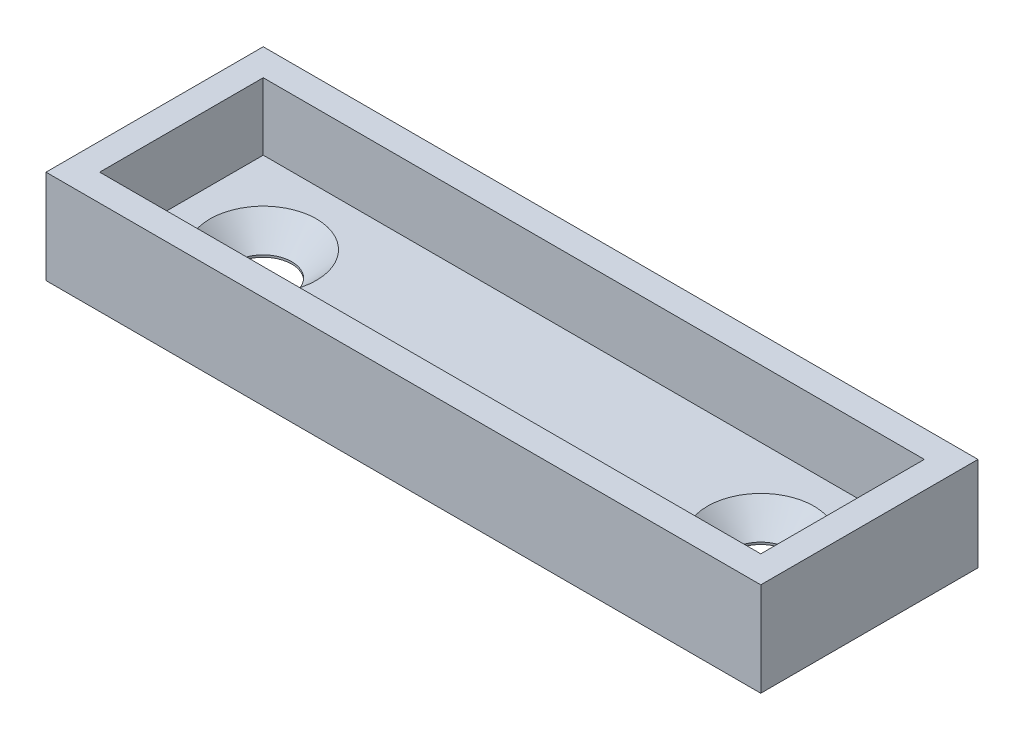
SolidWorks part; units mm, degrees
ref_plane "Front" through (0, 0, 0) normal (0, 0, 1) x (1, 0, 0)
ref_plane "Top" through (0, 0, 0) normal (0, 1, 0) x (1, 0, 0)
ref_plane "Right" through (0, 0, 0) normal (1, 0, 0) x (0, 0, -1)
sketch "Sketch1" plane through (0, 0, 0) normal (0, 1, 0) x (1, 0, 0)
  line L1 (-24.638, -6.096) -> (24.638, -6.096)
  line L2 (-24.638, -6.096) -> (-24.638, 6.096)
  line L3 (-24.638, 6.096) -> (24.638, 6.096)
  line L4 (24.638, -6.096) -> (24.638, 6.096)
  line L5 (-24.638, -6.096) -> (24.638, 6.096) construction
  line L6 (-24.638, 6.096) -> (24.638, -6.096) construction
  point P0 (0, 0)
  point P8 (23.1563, -0.1012)
  dimension "D1" = 12.192
  dimension "D2" = 49.276
extrude "Boss-Extrude1" add sketch "Sketch1" along normal blind 2
sketch "Sketch2" plane through (0, 0, 0) normal (0, 1, 0) x (1, 0, 0)
  line L0 (24.638, 6.096) -> (26.638, 8.096) construction
  line L1 (-26.638, -8.096) -> (26.638, -8.096)
  line L2 (-26.638, -8.096) -> (-26.638, 8.096)
  line L3 (-26.638, 8.096) -> (26.638, 8.096)
  line L4 (24.638, -6.096) -> (24.638, 6.096)
  line L5 (24.638, 6.096) -> (-24.638, 6.096)
  line L6 (-24.638, 6.096) -> (-24.638, -6.096)
  line L7 (-24.638, -6.096) -> (24.638, -6.096)
  line L8 (24.638, -6.096) -> (24.638, 6.096)
  line L9 (24.638, 6.096) -> (-24.638, 6.096)
  line L10 (-24.638, 6.096) -> (-24.638, -6.096)
  line L11 (-24.638, -6.096) -> (24.638, -6.096)
  line L12 (26.638, -8.096) -> (26.638, 8.096)
  line L13 (-26.638, -8.096) -> (26.638, 8.096) construction
  line L14 (-26.638, 8.096) -> (26.638, -8.096) construction
  line L15 (-26.638, 8.096) -> (-24.638, 6.096) construction
  point P2 (0, 0)
  dimension "D2" = 2
  dimension "D1" = 0
extrude "Boss-Extrude2" add sketch "Sketch2" along normal offset from surface (7 mm away) 5 up to face at (0, 2, 0) offset beyond the face yes
sketch "Sketch3" plane through (0, 2, 0) normal (0, 1, 0) x (1, 0, 0)
  line L0 (-24.638, 6.096) -> (-18.542, 0) construction
  line L1 (-18.542, 0) -> (-24.638, -6.096) construction
  circle A0 centre (-18.542, 0) radius 2.1273
  dimension "D1" = 4.2545
extrude "Cut-Extrude1" cut sketch "Sketch3" against normal through all
ref_axis "Axis1" through (-18.542, 0, 0) along (0, 1, 0)
ref_plane "Plane1" through (0, 0, 0) normal (0, 0, -1) x (-1, 0, 0)
sketch "Sketch4" plane through (0, 0, 0) normal (0, 0, -1) x (-1, 0, 0)
  line L0 (16.4148, 1) -> (20.6693, 1) construction
  line L1 (16.4148, 2) -> (16.4148, 0) construction
  line L2 (20.6693, 0) -> (20.6693, 2) construction
  line L3 (18.542, 1) -> (18.542, 2)
  line L4 (-24.638, 2) -> (24.638, 2) construction
  line L5 (18.542, 2) -> (14.5733, 2)
  line L6 (14.5733, 2) -> (18.542, -1.9688)
  line L7 (18.542, -1.9688) -> (18.542, 1)
  line L8 (18.542, 2) -> (18.542, 3) construction
  dimension "D1" = 45
  dimension "D2" = 7.9375
revolve "Cut-Revolve1" cut sketch "Sketch4" angle 360 about L8
mirror "Mirror1" about plane through (0, 0, 0) normal (1, 0, 0) of "Cut-Revolve1", "Cut-Extrude1"
sketch "Sketch5" plane through (0, 0, 0) normal (0, -1, 0) x (-1, 0, 0)
  line L0 (0, 5.471) -> (0, -5.471) construction
  line L1 (26.638, -8.096) -> (-26.638, -8.096) construction
  line L2 (12.5, -3.846) -> (-12.5, -3.846)
  line L3 (12.5, -3.846) -> (12.5, -7.096)
  line L4 (12.5, -7.096) -> (-12.5, -7.096)
  line L5 (-12.5, -3.846) -> (-12.5, -7.096)
  line L6 (12.5, -3.846) -> (-12.5, -7.096) construction
  line L7 (12.5, -7.096) -> (-12.5, -3.846) construction
  line L8 (12.5, 7.096) -> (-12.5, 7.096)
  line L9 (12.5, 7.096) -> (12.5, 3.846)
  line L10 (12.5, 3.846) -> (-12.5, 3.846)
  line L11 (-12.5, 7.096) -> (-12.5, 3.846)
  line L12 (12.5, 7.096) -> (-12.5, 3.846) construction
  line L13 (12.5, 3.846) -> (-12.5, 7.096) construction
  point P3 (0, 0)
  point P12 (-13.4767, -6.7058)
  dimension "D1" = 3.25
  dimension "D2" = 1
  dimension "D3" = 25
extrude "Cut-Extrude2" cut sketch "Sketch5" against normal blind 0.6
